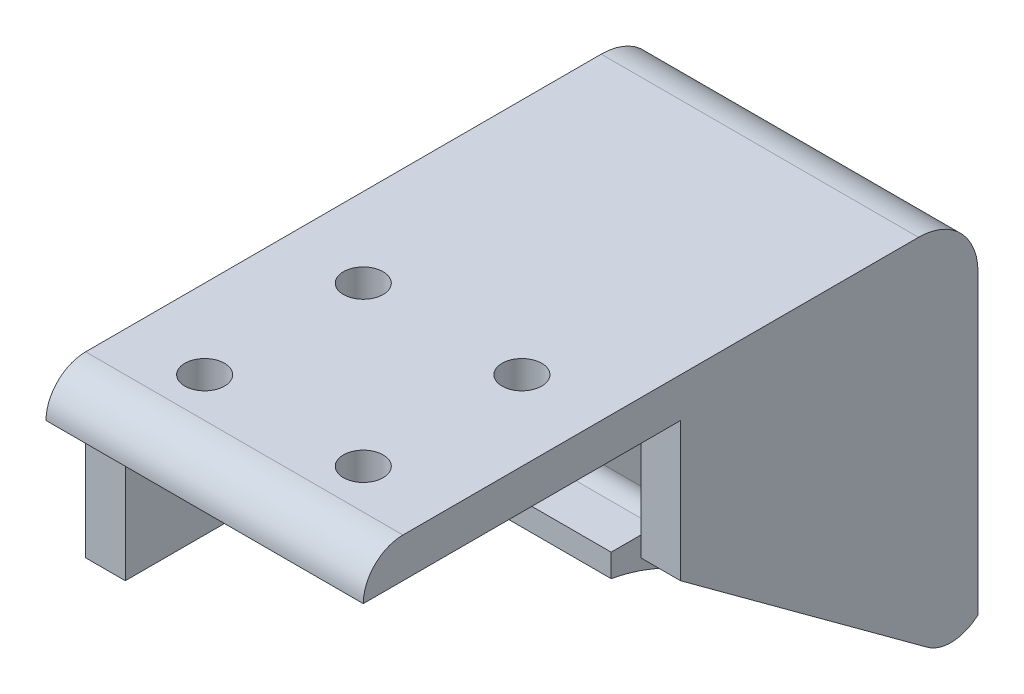
SolidWorks part; units mm, degrees
ref_plane "前视基准面" through (0, 0, 0) normal (0, 0, 1) x (1, 0, 0)
ref_plane "上视基准面" through (0, 0, 0) normal (0, 1, 0) x (1, 0, 0)
ref_plane "右视基准面" through (0, 0, 0) normal (1, 0, 0) x (0, 0, -1)
sketch "Sketch1" plane through (0, 0, 0) normal (0, 1, 0) x (1, 0, 0)
  line L1 (0, 0) -> (2, 0)
  line L2 (0, 0) -> (0, -14)
  line L3 (0, -14) -> (2, -14)
  line L4 (2, 0) -> (2, -14)
  line L5 (2, 0) -> (14, 0)
  line L6 (2, 0) -> (2, -2)
  line L7 (2, -2) -> (14, -2)
  line L8 (14, 0) -> (14, -2)
extrude "Boss-Extrude1" add sketch "Sketch1" along normal blind 7 contours L1 L2 L3 L4
sketch "Sketch2" plane through (0, 7, 0) normal (0, 1, 0) x (1, 0, 0)
  line L9 (0, 0) -> (16, 0)
  line L10 (0, 0) -> (0, -16)
  line L11 (0, -16) -> (16, -16)
  line L12 (16, 0) -> (16, -16)
extrude "Boss-Extrude2" add sketch "Sketch2" along normal blind 2
sketch "Sketch4" plane through (16, 0, 0) normal (1, 0, 0) x (0, 0, -1)
  line L0 (0, 0) -> (15, -11)
  line L1 (0, 9) -> (15, 9)
  line L2 (0, 9) -> (0, 0)
  line L9 (15, 9) -> (15, -11)
extrude "Boss-Extrude3" add sketch "Sketch4" against normal blind 2
sketch "Sketch5" plane through (0, 0, 0) normal (-1, 0, 0) x (0, 0, 1)
  line L0 (0, 9) -> (-15, 9)
  line L1 (-15, 9) -> (-15, -11)
  line L2 (0, 0) -> (-15, -11) construction
  line L3 (-15, -11) -> (-15, 9) construction
  line L4 (-15, -11) -> (0, 0)
  line L5 (0, 0) -> (0, 9)
extrude "Boss-Extrude4" add sketch "Sketch5" against normal blind 2
sketch "Sketch6" plane through (0, 9, 0) normal (0, 1, 0) x (1, 0, 0)
  line L1 (14, 0) -> (2, 0)
  line L2 (14, 0) -> (14, 15)
  line L3 (14, 15) -> (2, 15)
  line L4 (2, 0) -> (2, 15)
extrude "Boss-Extrude5" add sketch "Sketch6" against normal blind 2
sketch "Sketch7" plane through (0, 0, -15) normal (0, 0, -1) x (-1, 0, 0)
  line L1 (-14, 7) -> (-2, 7)
  line L2 (-14, 7) -> (-14, -9)
  line L3 (-14, -9) -> (-2, -9)
  line L4 (-2, 7) -> (-2, -9)
extrude "Boss-Extrude6" add sketch "Sketch7" against normal blind 2
sketch "Sketch8" plane through (0, 0, 0) normal (0, -0.8064, 0.5914) x (1, 0, 0)
  line L1 (14, 0) -> (2, 0)
  line L2 (14, 0) -> (14, -17)
  line L3 (14, -17) -> (2, -17)
  line L4 (2, 0) -> (2, -17)
extrude "Boss-Extrude7" add sketch "Sketch8" against normal blind 2
sketch "Sketch9" plane through (0, 0, 0) normal (0, -1, 0) x (1, 0, 0)
  line L0 (2, 0) -> (2, 1.5) construction
  line L9 (2, -13) -> (2, 14) construction
  line L11 (2, 1.5) -> (14, 1.5)
  line L12 (2, 1.5) -> (2, -2)
  line L13 (2, -2) -> (14, -2)
  line L14 (14, 1.5) -> (14, -2)
extrude "Boss-Extrude9" add sketch "Sketch9" against normal blind 1
fillet "Fillet1" radius 3 1 edges at (8, 9, -15)
fillet "Fillet2" radius 10 1 edges at (7, 0, 0)
fillet "Fillet3" radius 2 1 edges at (8, 9, 16)
sketch "Sketch14" plane through (0, 9, 0) normal (0, 1, 0) x (1, 0, 0)
  line L0 (0, -14) -> (4, -14) construction
  line L1 (0, -14) -> (16, -14) construction
  line L2 (4, -14) -> (4, -12) construction
  line L3 (16, -14) -> (12, -14) construction
  line L4 (12, -14) -> (12, -12) construction
  line L5 (4, -12) -> (4, -4) construction
  line L6 (12, -12) -> (12, -4) construction
  circle A0 centre (4, -12) radius 1
  circle A1 centre (4, -4) radius 1
  circle A2 centre (12, -12) radius 1
  circle A3 centre (12, -4) radius 1
  point P16 (0, 0)
extrude "Cut-Extrude4" cut sketch "Sketch14" against normal up to next
fillet "Fillet4" radius 2 1 edges at (8, 1.6128, -1.1827)
sketch "Sketch15" plane through (16, 0, 0) normal (1, 0, 0) x (0, 0, -1)
  line L0 (15, -11) -> (15, -9)
  line L1 (15, -11) -> (15, 6) construction
  line L2 (15, -9) -> (12.2727, -9)
  line L3 (0, 0) -> (15, -11) construction
  line L4 (12.2727, -9) -> (15, -11)
  line L5 (15, -9) -> (13.6364, -10)
  line M6 (15, -11) -> (15, 6)
extrude "Cut-Extrude5" cut sketch "Sketch15" against normal through all contours L5 L4 M6
fillet "Fillet5" radius 2 1 edges at (8, -10, -13.6364)
